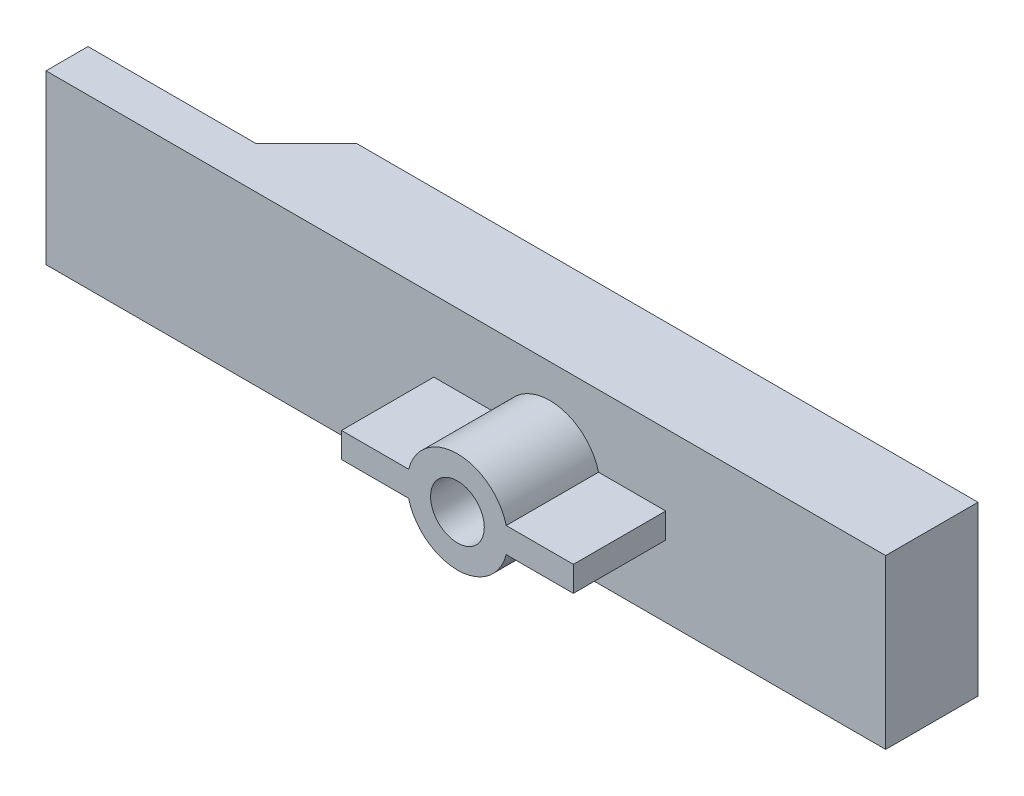
SolidWorks part; units mm, degrees
ref_plane "前视基准面" through (0, 0, 0) normal (0, 0, 1) x (1, 0, 0)
ref_plane "上视基准面" through (0, 0, 0) normal (0, 1, 0) x (1, 0, 0)
ref_plane "右视基准面" through (0, 0, 0) normal (1, 0, 0) x (0, 0, -1)
sketch "草图1" plane through (0, 0, 0) normal (0, 0, 1) x (1, 0, 0)
  line L1 (0, 0) -> (40, 0)
  line L2 (0, 0) -> (0, 10)
  line L3 (0, 10) -> (40, 10)
  line L4 (40, 0) -> (40, 10)
  line L5 (0, 0) -> (40, 10) construction
  line L6 (0, 10) -> (40, 0) construction
  point P4 (20, 5)
  dimension "D1" = 40
  dimension "D2" = 10
extrude "凸台-拉伸1" add sketch "草图1" along normal blind 2.5
sketch "草图2" plane through (0, 0, 2.5) normal (0, 0, 1) x (1, 0, 0)
  line L0 (40, 10) -> (0, 10) construction
  line L1 (17.5, 10) -> (22.5, 10)
  line L2 (17.5, 10) -> (17.5, 0)
  line L3 (17.5, 0) -> (22.5, 0)
  line L4 (22.5, 10) -> (22.5, 0)
  line L5 (17.5, 10) -> (22.5, 0) construction
  line L6 (17.5, 0) -> (22.5, 10) construction
  line L7 (0, 0) -> (40, 0) construction
  line L8 (20, 10) -> (20, 0) construction
  point P4 (20, 5)
  dimension "D1" = 5
sketch "草图3" plane through (0, 0, 0) normal (0, 0, -1) x (-1, 0, 0)
  line L0 (0, 0) -> (-40, 0) construction
  line L1 (-40, 10) -> (-36, 10)
  line L2 (-40, 10) -> (-40, 0)
  line L3 (-40, 0) -> (-36, 0)
  line L4 (-36, 10) -> (-36, 0)
  line L5 (-40, 10) -> (-36, 0) construction
  line L6 (-40, 0) -> (-36, 10) construction
  point P4 (-38, 5)
  dimension "D1" = 4
extrude "凸台-拉伸3" add sketch "草图3" along normal blind 3
sketch "草图4" plane through (0, 0, 0) normal (0, 0, -1) x (-1, 0, 0)
  line L0 (-36, 0) -> (-36, 10) construction
  line L1 (-36, 6.5) -> (0, 6.5)
  line L2 (-36, 6.5) -> (-36, 3.5)
  line L3 (-36, 3.5) -> (0, 3.5)
  line L4 (0, 6.5) -> (0, 3.5)
  line L5 (0, 10) -> (0, 0) construction
  line L6 (-36, 5) -> (0, 5) construction
  line L7 (-36, 0) -> (-36, 10) construction
  line L8 (0, 0) -> (-36, 0) construction
  line L9 (0, 10) -> (-3, 10)
  line L10 (0, 10) -> (0, 0)
  line L11 (0, 0) -> (-3, 0)
  line L12 (-3, 10) -> (-3, 0)
  line L13 (-36, 10) -> (0, 10) construction
  line L14 (-21, 10) -> (-18, 10)
  line L15 (-21, 10) -> (-21, 0)
  line L16 (-21, 0) -> (-18, 0)
  line L17 (-18, 10) -> (-18, 0)
  line M6 (-36, 10) -> (-36, 0)
  line M7 (-36, 0) -> (0, 0)
  line M8 (0, 0) -> (0, 10)
  line M9 (0, 10) -> (-36, 10)
  dimension "D1" = 3
  dimension "D2" = 3
  dimension "D3" = 3
  dimension "D4" = 18
extrude "凸台-拉伸4" add sketch "草图4" along normal up to surface (3 mm away) contours L6 L15 L1 M6 | L6 L2 L3 L15 | L15 L6 L17 L1 | L6 L15 L3 L17 | L17 L15 L1 M9 | L17 L3 L15 M7 | L17 L6 L12 L1 | L6 L17 L3 L12 | L12 L6 L10 L1 | L6 L12 L3 M8 | L12 L1 M9 M8 | L3 L12 M7 M8 region at (28.5, 5.75, 0) region at (19.5, 8.25, 0) region at (19.5, 5.75, 0) region at (28.5, 4.25, 0) region at (10.5, 5.75, 0) region at (19.5, 4.25, 0) region at (1.5, 8.25, 0) region at (1.5, 5.75, 0) region at (10.5, 4.25, 0) region at (19.5, 1.75, 0) region at (1.5, 4.25, 0) region at (1.5, 1.75, 0) up to face at (38, 5, -3)
chamfer "倒角1" distance 1.5 angle 45 4 edges at (10.5, 3.5, -3) (28.5, 3.5, -3) (10.5, 3.5, 0) (28.5, 3.5, 0)
sketch "草图6" plane through (0, 0, 2.5) normal (0, 0, 1) x (1, 0, 0)
  line L0 (0, 5) -> (40, 5) construction
  line L1 (0, 10) -> (0, 0) construction
  line L3 (40, 0) -> (40, 10) construction
  circle A0 centre (20, 5) radius 1.6
  circle A2 centre (20, 5) radius 3
  dimension "D1" = 3.2
  dimension "D3" = 6
extrude "凸台-拉伸5" add sketch "草图6" along normal blind 5.5
sketch "草图7" plane through (0, 0, 0) normal (-1, 0, 0) x (0, 0, 1)
  line L1 (0, 0) -> (2.5, 0)
  line L2 (0, 0) -> (0, 10)
  line L3 (0, 10) -> (2.5, 10)
  line L4 (2.5, 0) -> (2.5, 10)
extrude "凸台-拉伸6" add sketch "草图7" along normal blind 10
sketch "草图8" plane through (0, 0, 2.5) normal (0, 0, 1) x (1, 0, 0)
  line L0 (20, 8) -> (20, 2) construction
  line L1 (17.0953, 5.75) -> (13.0953, 5.75)
  line L2 (17.0953, 5.75) -> (17.0953, 4.25)
  line L3 (17.0953, 4.25) -> (13.0953, 4.25)
  line L4 (13.0953, 5.75) -> (13.0953, 4.25)
  line L5 (26.9047, 5.75) -> (26.9047, 4.25)
  line L6 (22.9047, 4.25) -> (26.9047, 4.25)
  line L7 (22.9047, 5.75) -> (22.9047, 4.25)
  line L8 (22.9047, 5.75) -> (26.9047, 5.75)
  circle A0 centre (20, 5) radius 3 construction
  circle A1 centre (20, 5) radius 3 construction
  dimension "D1" = 4
  dimension "D2" = 1.5
extrude "凸台-拉伸7" add sketch "草图8" along normal up to surface (5.5 mm away) up to face at (23, 5, 8)
sketch "草图9" plane through (0, 0, 0) normal (0, 0, -1) x (-1, 0, 0)
  line L1 (-3, 0) -> (-36, 0)
  line L2 (-3, 0) -> (-3, 10)
  line L3 (-3, 10) -> (-36, 10)
  line L4 (-36, 0) -> (-36, 10)
extrude "凸台-拉伸8" add sketch "草图9" along normal up to surface (3 mm away) up to face at (19.6, 5.3, -3)
chamfer "倒角2" distance 3 angle 45 1 edges at (0, 5, -3)
